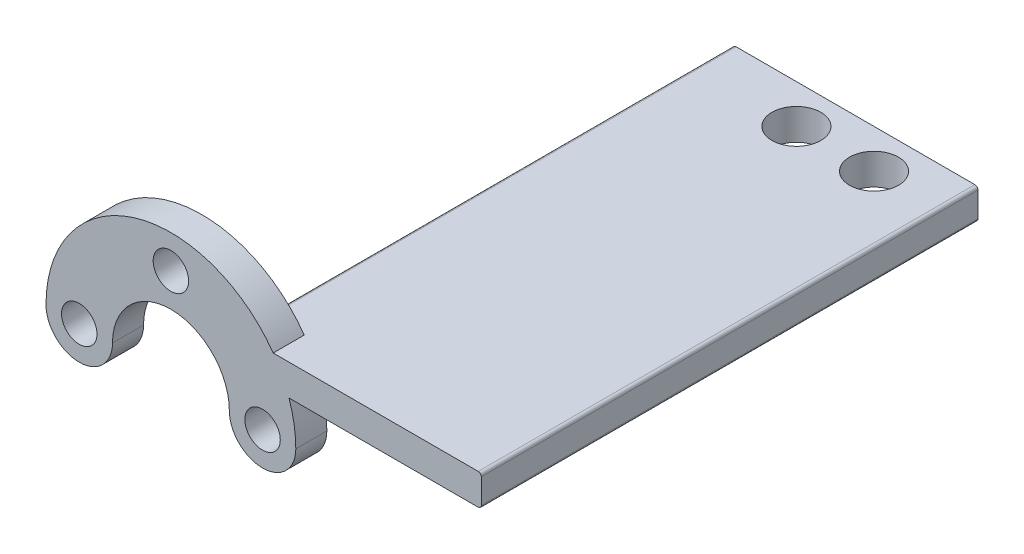
SolidWorks part; units mm, degrees
note: The reader was unsure of these and kept them because the rebuilt part matched: shared geometry of "Sketch1<3>".
ref_plane "Front Plane" through (0, 0, 0) normal (0, 0, 1) x (1, 0, 0)
ref_plane "Top Plane" through (0, 0, 0) normal (0, 1, 0) x (1, 0, 0)
ref_plane "Right Plane" through (0, 0, 0) normal (1, 0, 0) x (0, 0, -1)
sketch "Sketch1" plane through (0, 0, 0) normal (0, 0, 1) x (1, 0, 0)
  line L3 (-7.5, 0) -> (7.5, 0)
  line L4 (0, 7.5) -> (0, -7.5)
  line L6 (0, 0) -> (20.32, 0)
  line L7 (0, 0) -> (0, 3.3274)
  line L8 (0, 3.3274) -> (20.32, 3.3274)
  line L9 (20.32, 0) -> (20.32, 3.3274)
  line L10 (0, 3.3274) -> (25.4, 3.3274)
  line L11 (0, 3.3274) -> (0, 5.8674)
  line L12 (0, 5.8674) -> (25.4, 5.8674)
  line L13 (25.4, 3.3274) -> (25.4, 5.8674)
  circle A0 centre (-7.5, 0) radius 1.45
  circle A1 centre (0, -7.5) radius 1.45
  circle A2 centre (7.5, 0) radius 1.45
  circle A4 centre (0, 7.5) radius 1.45
  circle A6 centre (0, 7.5) radius 2.72
  circle A7 centre (-7.5, 0) radius 2.72
  circle A8 centre (7.5, 0) radius 2.72
  circle A9 centre (0, 0) radius 4.78
  circle A10 centre (0, 0) radius 10.22
  circle A11 centre (0, 0) radius 6.41
  circle A12 centre (0, 0) radius 7.68
  point P3 (0, 0)
  point P8 (0, 0)
  dimension "D2" = 2.9
  dimension "D3" = 2.9
  dimension "D4" = 2.9
  dimension "D6" = 3.3274
  dimension "D8" = 2.9
  dimension "D1" = 1.27
  dimension "D5" = 15
  dimension "D7" = 20.32
  dimension "D9" = 2.54
  dimension "D10" = 3.81
  dimension "D11" = 25.4
  dimension "D12" = 2.54
extrude "Boss-Extrude1" add sketch "Sketch1" along normal blind 2.54
extrude "Boss-Extrude2" add sketch "Sketch1<3>" against normal blind 38.1 contours A10 L8 L13 L12 | A11 L8 A10 L12
sketch "Sketch1<3>" plane through (0, 0, 0) normal (0, 0, 1) x (1, 0, 0) same geometry as "Sketch1"
fillet "Fillet1" radius 0.254 4 edges at (25.4, 5.8674, -17.78) (25.4, 3.3274, -17.78) (6.9218, 3.3274, -19.05) (4.9554, 5.8674, -19.05)
sketch "Sketch5" plane through (0, 5.8674, 0) normal (0, 1, 0) x (1, 0, 0)
  line L0 (5.607, 38.1) -> (25.146, 38.1) construction
  line L1 (5.607, 38.1) -> (25.146, 38.1)
  line L2 (5.607, 34.925) -> (25.146, 34.925)
  line L3 (25.146, 34.925) -> (25.146, 38.1)
  line L4 (5.607, 34.925) -> (5.607, 38.1)
  line L5 (20.066, 38.1) -> (20.066, 34.925)
  circle A0 centre (20.066, 34.925) radius 2.0002
  circle A1 centre (13.716, 34.925) radius 2.0002
  dimension "D2" = 4.0005
  dimension "D3" = 4.0005
  dimension "D4" = 5.08
  dimension "D5" = 6.35
  dimension "D1" = 3.175
extrude "Cut-Extrude1" cut sketch "Sketch5" against normal blind 19.05 contours L2 A0 | L5 A0 L2 | L2 A0 L5 | L2 A1 | L2 A1
